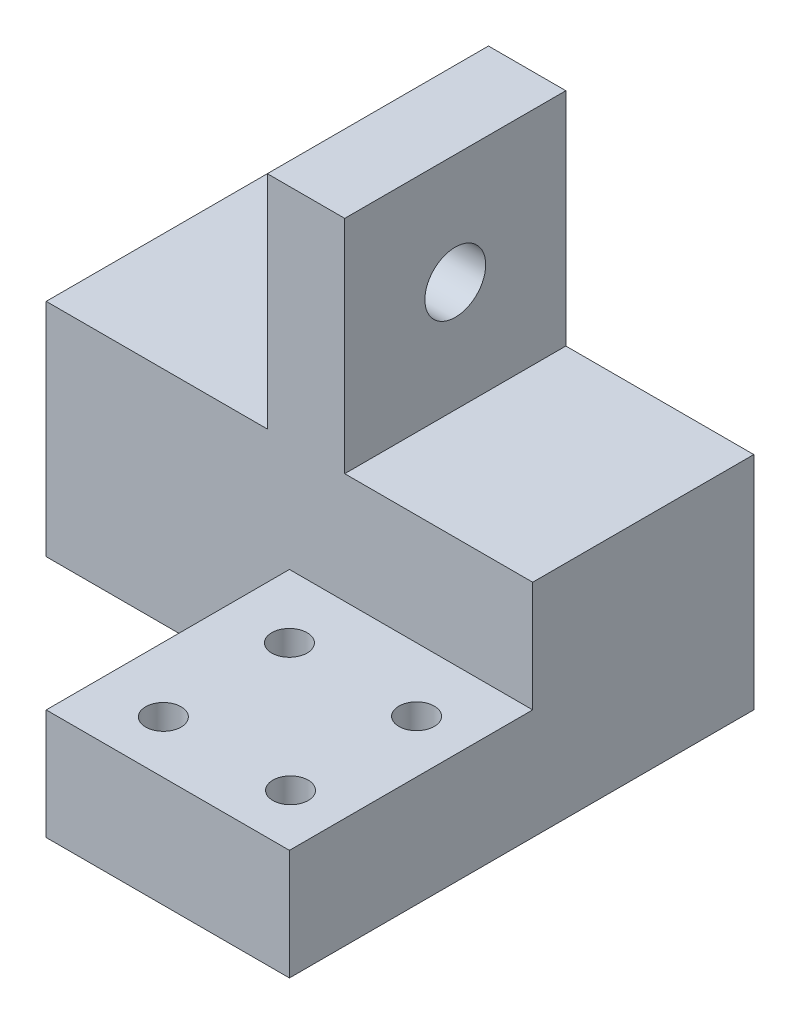
SolidWorks part; units mm, degrees
ref_plane "Front Plane" through (0, 0, 0) normal (0, 0, 1) x (1, 0, 0)
ref_plane "Top Plane" through (0, 0, 0) normal (0, 1, 0) x (1, 0, 0)
ref_plane "Right Plane" through (0, 0, 0) normal (1, 0, 0) x (0, 0, -1)
sketch "Sketch1" plane through (0, 0, 0) normal (0, 1, 0) x (1, 0, 0)
  line L1 (-11, 11) -> (11, 11)
  line L2 (-11, 11) -> (-11, -11)
  line L3 (-11, -11) -> (11, -11)
  line L4 (11, 11) -> (11, -11)
  circle A0 centre (0, 0) radius 11 construction
  circle A1 centre (-5.25, 5.25) radius 1.6
  circle A2 centre (6.25, 5.25) radius 1.6
  circle A3 centre (6.3486, -6.25) radius 1.6
  circle A5 centre (-5.1514, -6.25) radius 1.6
  point P13 (6.3486, 5.7687)
  point P17 (6.3486, -5.1667)
  point P18 (-4.9137, -5.4573)
  point P19 (0, 0)
  dimension "D1" = 22
  dimension "D2" = 3.2
  dimension "D3" = 11.5
  dimension "D4" = 11.5
  dimension "D5" = 11.5
  dimension "D6" = 11.5
  dimension "D7" = 5.25
  dimension "D8" = 5.25
extrude "Boss-Extrude1" add sketch "Sketch1" along normal blind 10
sketch "Sketch2" plane through (0, 0, -11) normal (0, 0, -1) x (-1, 0, 0)
  line L1 (-11, 0) -> (33, 0)
  line L2 (-11, 0) -> (-11, 20)
  line L3 (-11, 20) -> (33, 20)
  line L4 (33, 0) -> (33, 20)
  dimension "D1" = 20
  dimension "D2" = 44
extrude "Boss-Extrude2" add sketch "Sketch2" along normal blind 20
sketch "Sketch3" plane through (0, 20, 0) normal (0, 1, 0) x (1, 0, 0)
  line L0 (-33, 11) -> (11, 11) construction
  line L1 (-13, 11) -> (-6, 11)
  line L2 (-13, 11) -> (-13, 31)
  line L3 (-13, 31) -> (-6, 31)
  line L4 (-6, 11) -> (-6, 31)
  line L5 (11, 31) -> (11, 11) construction
  dimension "D1" = 20
  dimension "D2" = 7
  dimension "D3" = 17
extrude "Boss-Extrude3" add sketch "Sketch3" along normal blind 20
sketch "Sketch4" plane through (-6, 0, 0) normal (1, 0, 0) x (0, 0, -1)
  line L0 (11, 20) -> (31, 20) construction
  line L1 (31, 40) -> (31, 20) construction
  circle A0 centre (21, 30) radius 2.75
  point P6 (31, 30)
  dimension "D1" = 5.5
  dimension "D3" = 10
  dimension "D2" = 10
extrude "Cut-Extrude1" cut sketch "Sketch4" against normal through all
